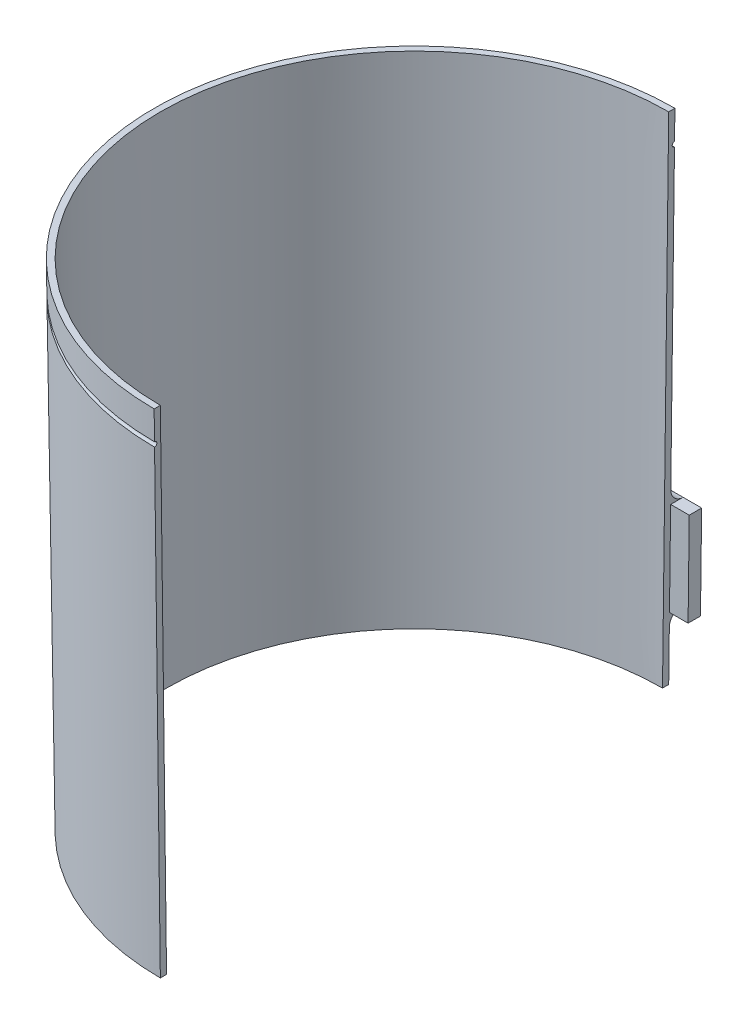
SolidWorks part; units mm, degrees
material "ABS"
ref_plane "Front" through (0, 0, 0) normal (0, 0, 1) x (1, 0, 0)
ref_plane "Top" through (0, 0, 0) normal (0, 1, 0) x (1, 0, 0)
ref_plane "Right" through (0, 0, 0) normal (1, 0, 0) x (0, 0, -1)
sketch "Эскиз1" plane through (0, 0, 0) normal (0, 1, 0) x (1, 0, 0)
  line L0 (0, 40) -> (0, 41)
  line L1 (0, -40) -> (0, -41)
  arc A0 (0, 41) -> (0, -41) centre (0, 0) ccw
  arc A1 (0, 40) -> (0, -40) centre (0, 0) ccw
  dimension "D1" = 82
  dimension "D2" = 80
ref_plane "Плоскость1" through (0, 80, 0) normal (0, 1, 0) x (1, 0, 0)
sketch "Эскиз2" plane through (0, 80, 0) normal (0, 1, 0) x (1, 0, 0)
  line L0 (0, 42) -> (0, 41)
  line L1 (0, -41) -> (0, -42)
  arc A0 (0, 42) -> (0, -42) centre (0, 0) ccw
  arc A1 (0, 41) -> (0, -41) centre (0, 0) ccw
  dimension "D1" = 84
  dimension "D2" = 82
loft "По сечениям1" add profiles "Эскиз1", "Эскиз2" connector at (0, 0, -40) connector at (0, 80, -41)
ref_plane "Плоскость2" through (-40.9936, -0.5124, 0) normal (-0.9999, -0.0125, 0) x (0, 0, 1)
sketch "Эскиз3" plane through (-40.9936, -0.5124, 0) normal (-0.9999, -0.0125, 0) x (0, 0, 1)
  line L1 (-1.5, 2.0121) -> (1.5, 2.0121)
  line L2 (-1.5, 2.0121) -> (-1.5, 0.5121)
  line L3 (-1.5, 0.5121) -> (1.5, 0.5121)
  line L4 (1.5, 2.0121) -> (1.5, 0.5121)
  line L5 (-1.5, 2.0121) -> (1.5, 0.5121) construction
  line L6 (-1.5, 0.5121) -> (1.5, 2.0121) construction
  ellipse E0 centre (0, 0) end of major axis (41, 0) minor radius 0.5125 (41, 0) -> (-41, 0) ccw construction
  point P0 (0, 1.2621)
  dimension "D1" = 1.5
  dimension "D2" = 3
  dimension "D3" = 0
extrude "Бобышка-Вытянуть1" add sketch "Эскиз3" along normal blind 2 and the other way up to surface other way up to face at (0, 20, -20.75)
chamfer "Фаска1" distance 1.5 distance2 1 1 edges at (-42.9998, -0.0253, 0) first distance on face at (-42.493, -0.019, -0.375)
ref_plane "Плоскость3" through (-5, 0, 0) normal (1, 0, 0) x (0, 0, -1)
sketch "Эскиз4" plane through (-5, 0, 0) normal (1, 0, 0) x (0, 0, -1)
  line L0 (41.3125, 25) -> (43.3127, 25)
  line L2 (41, 0) -> (42, 80) construction
  line L3 (43.3127, 25) -> (43.1252, 10)
  line L4 (43.1252, 10) -> (41.125, 10)
  line L5 (41.125, 10) -> (41.3125, 25)
  dimension "D1" = 2
  dimension "D2" = 10
  dimension "D3" = 15
extrude "Бобышка-Вытянуть2" add sketch "Эскиз4" along normal blind 8 separate body
sketch "Эскиз5" plane through (0, -0.5374, -42.9934) normal (0, -0.0125, -0.9999) x (-1, 0, 0)
  line L0 (-3, 25.5394) -> (5, 25.5394) construction
  line L1 (0, 25.5394) -> (5, 25.5394)
  line L2 (0, 25.5394) -> (0, 10.4535)
  line L3 (0, 10.4535) -> (5, 10.4535)
  line L4 (5, 25.5394) -> (5, 10.4535)
  line L5 (0, 0.5125) -> (0, 80.5187) construction
  line L6 (5, 50) -> (5, -50) construction
extrude "Бобышка-Вытянуть3" add sketch "Эскиз5" against normal up to next
fillet "Скругление1" radius 2 3 edges at (-2.5046, 9.9412, -41.0479) (-2.5046, 25.0259, -41.2368)
ref_axis "Ось1" through (0, -0.0001, 0) along (0, -1, 0)
sketch "Эскиз6" plane through (0, 0, 0) normal (1, 0, 0) x (0, 0, -1)
  line L0 (-41, 0) -> (-42, 80) construction
  line L1 (-42, 80) -> (-41, 80) construction
  circle A0 centre (-41.9375, 75) radius 0.375
  dimension "D1" = 0.75
  dimension "D2" = 0
  dimension "D3" = 5
revolve "Вырез-Повернуть1" cut sketch "Эскиз6" angle 360 about axis through (0, -0.0001, 0) along (0, -1, 0)
